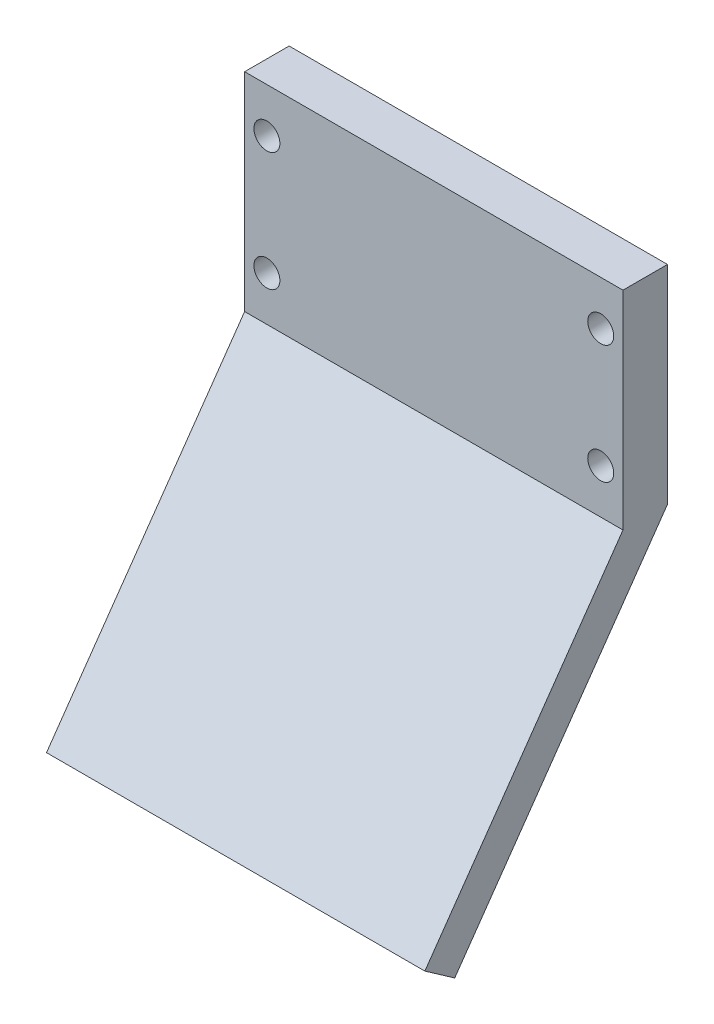
SolidWorks part; units mm, degrees
ref_plane "Plan de face" through (0, 0, 0) normal (0, 0, 1) x (1, 0, 0)
ref_plane "Plan de dessus" through (0, 0, 0) normal (0, 1, 0) x (1, 0, 0)
ref_plane "Plan de droite" through (0, 0, 0) normal (1, 0, 0) x (0, 0, -1)
sketch "Esquisse1" plane through (0, 0, 0) normal (0, 0, 1) x (1, 0, 0)
  line L1 (0, 0) -> (51, 0)
  line L2 (0, 0) -> (0, 28)
  line L3 (0, 28) -> (51, 28)
  line L4 (51, 0) -> (51, 28)
  dimension "D1" = 51
  dimension "D2" = 28
extrude "Boss.-Extru.1" add sketch "Esquisse1" along normal blind 6
sketch "Esquisse2" plane through (0, 0, 6) normal (0, 0, 1) x (1, 0, 0)
  line L0 (25.5, 0) -> (25.5, 22.4593) construction
  line L1 (0, 0) -> (51, 0) construction
  line L2 (3, 6) -> (3, 22) construction
  line L3 (0, 28) -> (0, 0) construction
  line L4 (48, 6) -> (48, 22) construction
  circle A0 centre (3, 6) radius 1.75
  circle A1 centre (3, 22) radius 1.75
  circle A2 centre (48, 22) radius 1.75
  circle A3 centre (48, 6) radius 1.75
  dimension "D4" = 3.5
  dimension "D1" = 16
  dimension "D2" = 3
  dimension "D3" = 6
extrude "Enlèv. mat.-Extru.1" cut sketch "Esquisse2" against normal through all
sketch "Esquisse3" plane through (0, 0, 0) normal (-1, 0, 0) x (0, 0, 1)
  line L0 (0, 0) -> (28.6788, -40.9576)
  line L1 (28.6788, -40.9576) -> (32.7049, -38.1385)
  line L2 (32.7049, -38.1385) -> (6, 0)
  line L3 (6, 0) -> (0, 0)
  line L4 (6, 28) -> (6, 0) construction
  point P3 (0, -20.2288)
  point P7 (11.6742, -20.0674)
  point P8 (17.5649, -14.4995)
  dimension "D1" = 50
  dimension "D2" = 145
extrude "Boss.-Extru.2" add sketch "Esquisse3" against normal up to vertex (51 mm away) up to point (51, 28, 6)
